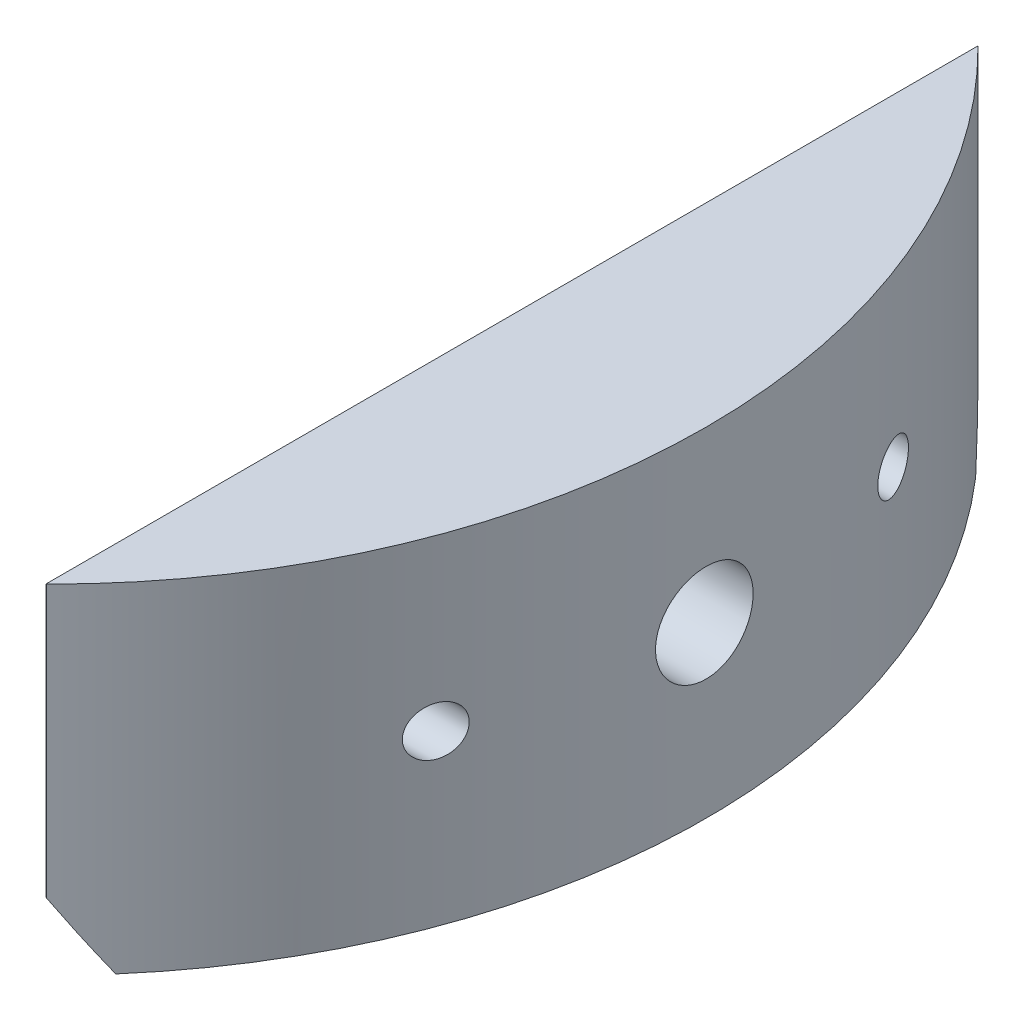
SolidWorks part; units mm, degrees
material "Plain Carbon Steel"
ref_plane "Front Plane" through (0, 0, 0) normal (0, 0, 1) x (1, 0, 0)
ref_plane "Top Plane" through (0, 0, 0) normal (0, 1, 0) x (1, 0, 0)
ref_plane "Right Plane" through (0, 0, 0) normal (1, 0, 0) x (0, 0, -1)
sketch "Sketch2" plane through (0, 0, 0) normal (0, 1, 0) x (1, 0, 0)
  line L0 (34.6715, 34.925) -> (34.6715, -34.925)
  line L2 (34.6715, 34.925) -> (34.6461, 34.925)
  line L3 (34.6715, 34.925) -> (34.6715, -34.925)
  line L4 (34.6715, -34.925) -> (34.6461, -34.925)
  line L5 (34.6461, 34.925) -> (34.6461, -34.925)
  line L13 (0, 0) -> (29.3279, 0) construction
  line L14 (0, 0) -> (47.5356, -12.7371) construction
  arc A0 (34.6715, -34.925) -> (34.6715, 34.925) centre (0, 0) ccw
  point P9 (34.6461, 0)
  dimension "D1" = 49.2125
  dimension "D2" = 69.85
  dimension "D3" = 0.0254
  dimension "D6" = 15
extrude "Boss-Extrude1" add sketch "Sketch2" along normal blind 25.4 contours L2 L5 L4 L0 | L0 A0 | L0 A0 region at (40.5685, 0, 0) region at (34.6588, 0, 0)
ref_plane "Plane1" through (49.2125, 0, 0) normal (1, 0, 0) x (0, 0, -1)
sketch "Sketch4" plane through (34.6461, 0, 0) normal (-1, 0, 0) x (0, 0, 1)
  line L0 (-34.925, 12.7) -> (34.925, 12.7) construction
  line L1 (-34.925, 25.4) -> (-34.925, 0) construction
  line L2 (0, 25.4) -> (0, 0) construction
  line L4 (-34.925, 0) -> (34.925, 0)
  line L10 (34.925, 0) -> (34.925, 25.4)
  line L11 (34.925, 25.4) -> (-34.925, 25.4)
  line L12 (-34.925, 25.4) -> (-34.925, 0)
  line L13 (-34.925, 0) -> (34.925, 0)
  line L14 (34.925, 0) -> (34.925, 25.4)
  line L15 (34.925, 25.4) -> (-34.925, 25.4)
  line L16 (-34.925, 25.4) -> (-34.925, 0)
  circle A0 centre (0, 12.7) radius 3.81
  circle A1 centre (0, 12.7) radius 1.27
  point P11 (0, 0)
  point P15 (0, 12.7)
  dimension "D1" = 7.62
  dimension "D2" = 2.54
  dimension "D3" = 0
extrude "Cut-Extrude2" cut sketch "Sketch4" against normal up to next contours A1
sketch "Sketch11" plane through (34.6461, 0, 0) normal (-1, 0, 0) x (0, 0, 1)
  circle A2 centre (0, 12.7) radius 3.6576
  dimension "D3" = 7.3152
extrude "Cut-Extrude4" cut sketch "Sketch11" along normal blind 7.62 from surface contours A2 starting at plane "Plane1"
sketch "Sketch13" plane through (49.2125, 0, 0) normal (1, 0, 0) x (0, 0, -1)
  line L1 (-6.2992, 12.7) -> (-7.6327, 12.7) construction
  line L2 (-6.2992, 12.7) -> (-4.9657, 12.7) construction
  line L4 (0, 12.7) -> (-34.925, 12.7) construction
  line L5 (-34.925, 25.4) -> (-34.925, 0) construction
  circle A0 centre (0, 12.7) radius 4.9657
  circle A1 centre (0, 12.7) radius 7.6327
  circle A2 centre (0, 12.7) radius 6.2992 construction
  dimension "D1" = 12.5984
  dimension "D2" = 2.667
wrap "Wrap3" [suppressed] sketch "Sketch13" source sketch "Sketch13" thickness 1.3208 parameters "D1"=1.3208
sketch "Sketch15" plane through (0, 0, 0) normal (1, 0, 0) x (0, 0, -1)
  line L0 (-34.925, 12.7) -> (34.925, 12.7) construction
  line L1 (0, 0) -> (0, 25.4) construction
  line L4 (-34.925, 0) -> (34.925, 0)
  line L5 (34.925, 0) -> (34.925, 25.4)
  line L6 (-34.925, 0) -> (34.925, 0)
  line L7 (-34.925, 25.4) -> (-34.925, 0)
  line L9 (34.925, 0) -> (34.925, 25.4)
  line L11 (-34.925, 25.4) -> (-34.925, 0)
  line L14 (34.925, 25.4) -> (-34.925, 25.4)
  line L15 (34.925, 25.4) -> (-34.925, 25.4)
  circle A0 centre (-17.145, 12.7) radius 1.8288
  circle A1 centre (17.145, 12.7) radius 1.8288
  dimension "D2" = 3.6576
  dimension "D3" = 17.145
extrude "Cut-Extrude5" cut sketch "Sketch15" along normal up to surface (46.7684 mm away) contours L0 A0 | A1 region at (0, 12.7, 17.145) region at (0, 12.7, -17.145) up to face at (49.0834, 13.5299, 3.5622)
chamfer "Chamfer1" distance 2.54 distance2 5.08 1 edges at (34.6461, 0, 0) first distance on face at (38.2941, 0, 0)
equation "\"Middle Coupler Inner Daimeter\"= 3.875in"
equation "\"Middle Coupler  Wall Thickness\" = 0.25in"
equation "\"Middle Coupler Bottom Thickness\"= 0.2in"
equation "\"Bearing Rail Offset\"= 0.45in"
equation "\"3-56 UNF Tap\"= 0.089in"
equation "\"3-48 Tap\"= 0.079in"
equation "\"3-56 UNF Clearance\"= 0.104in"
equation "\"3-48 Clearance\" = 0.104in"
equation "\"Ball Bearing Distance\"= 0.03in"
equation "\"TCA Outer Diameter\" = 6in"
equation "\"Interstage Aeroframe Wall Thickness\" = 0.072in"
equation "\"Compression Spring OD\"= 0.42in"
equation "\"10-24 Tap\"= 0.157in"
equation "\"10-24 Clearance\"= 0.196in"
equation "\"Lower Stage Fuselage Wall Thickness\" = 0.25in"
equation "\"6-32 Tap\" = 0.107in"
equation "\"6-32 Clearance\" = 0.144"
equation "\"1/4-20 Tap\" = 0.201in"
equation "\"12-24 Tap\" = 0.177in"
equation "\"D1@Sketch2\"=\"Middle Coupler Inner Daimeter\"/2"
equation "\"D2@Sketch15\"=\"6-32 Clearance\""
